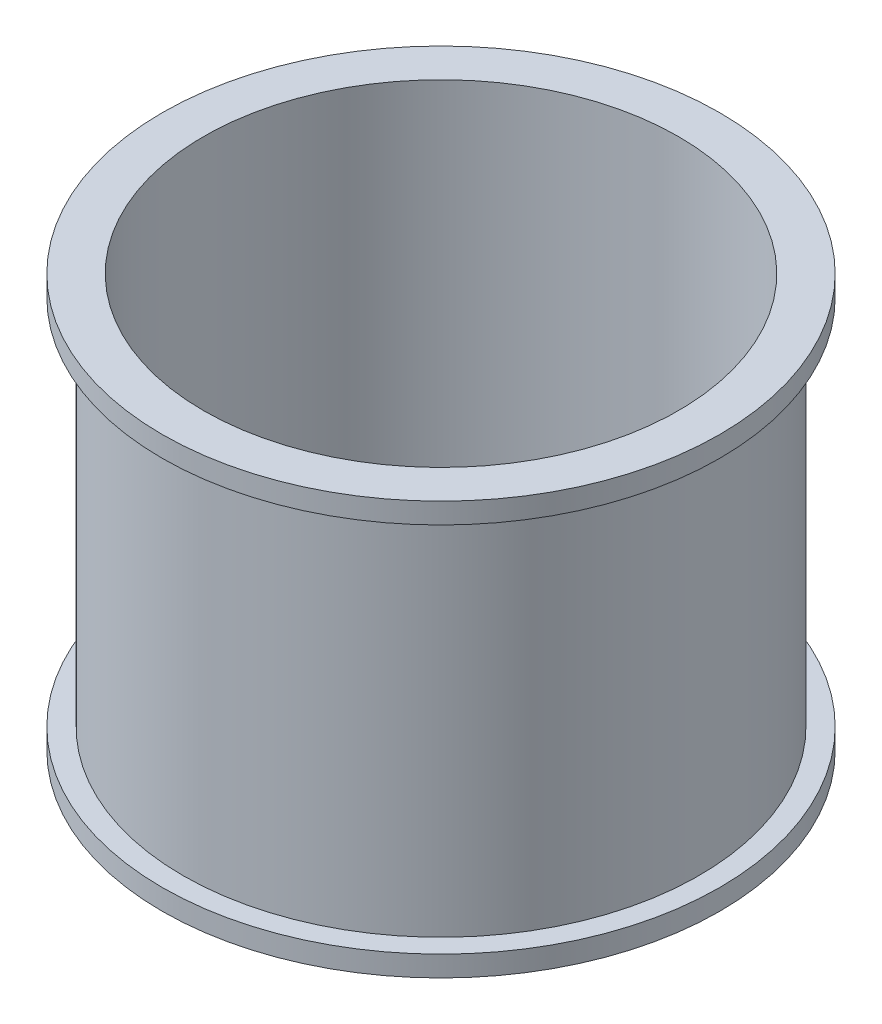
SolidWorks part; units mm, degrees
ref_plane "Front Plane" through (0, 0, 0) normal (0, 0, 1) x (1, 0, 0)
ref_plane "Top Plane" through (0, 0, 0) normal (0, 1, 0) x (1, 0, 0)
ref_plane "Right Plane" through (0, 0, 0) normal (1, 0, 0) x (0, 0, -1)
sketch "Sketch1" plane through (0, 0, 0) normal (0, 1, 0) x (1, 0, 0)
  circle A0 centre (0, 0) radius 5.75
  circle A1 centre (0, 0) radius 6.25
  circle A2 centre (0, 0) radius 6.75
  dimension "D1" = 11.5
  dimension "D2" = 12.5
  dimension "D3" = 0.5
extrude "Boss-Extrude1" add sketch "Sketch1" along normal blind 5 contours A1 A0 region at (-6.0732, 0, 0)
extrude "Boss-Extrude2" add sketch "Sketch1<3>" along normal blind 0.5 contours A2 A1 region at (-6.5591, 0, 0)
sketch "Sketch1<3>" plane through (0, 0, 0) normal (0, 1, 0) x (1, 0, 0) same geometry as "Sketch1"
mirror "Mirror1" about plane through (0, 5, 0) normal (0, 1, 0) of "Boss-Extrude1", "Boss-Extrude2"
